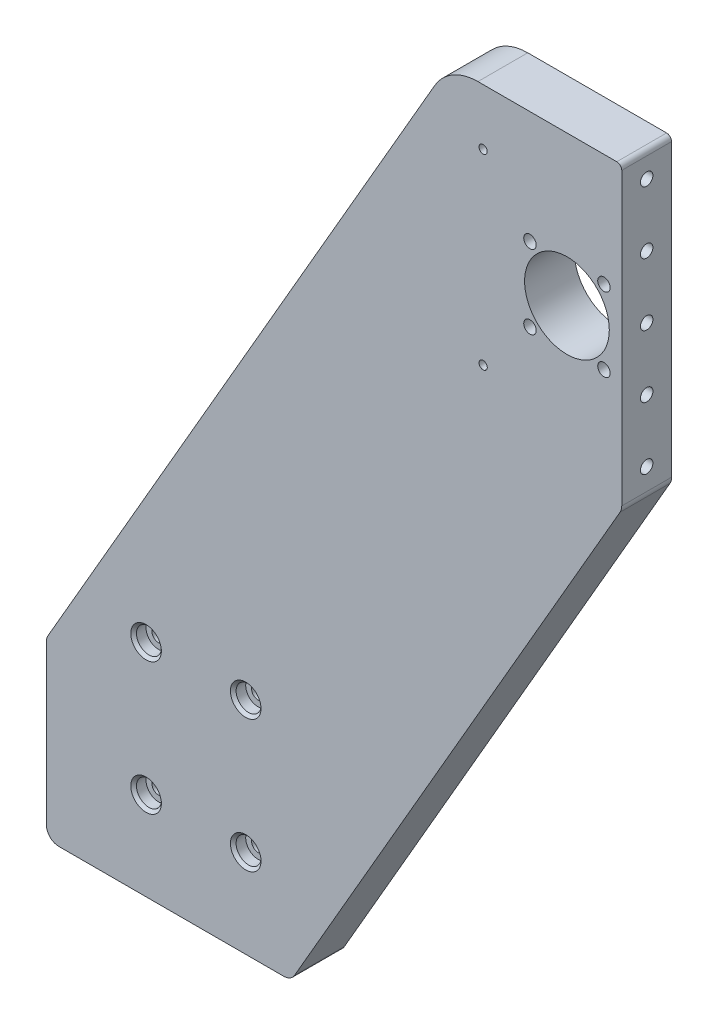
SolidWorks part; units mm, degrees
ref_plane "Piano frontale" through (0, 0, 0) normal (0, 0, 1) x (1, 0, 0)
ref_plane "Piano superiore" through (0, 0, 0) normal (0, 1, 0) x (1, 0, 0)
ref_plane "Piano destro" through (0, 0, 0) normal (1, 0, 0) x (0, 0, -1)
sketch "Schizzo1" plane through (0, 0, 0) normal (0, 0, 1) x (1, 0, 0)
  line L0 (5, 0) -> (95.2628, 0)
  line L1 (99.5929, 2.5) -> (230.2702, 228.8397)
  line L2 (230.9401, 231.3397) -> (230.9401, 348)
  line L3 (228.9401, 350) -> (173.2051, 350)
  line L4 (0, 68.6603) -> (0, 5)
  line L5 (155.8846, 340) -> (0.6699, 71.1603)
  line L9 (208.9401, 290) -> (194.0909, 304.8492) construction
  line L10 (208.9401, 290) -> (187.9401, 290) construction
  line L11 (208.9401, 290) -> (208.9401, 311) construction
  line L12 (50.1314, 0) -> (50.1314, 156.8301) construction
  circle A4 centre (208.9401, 290) radius 17
  circle A5 centre (208.9401, 290) radius 21 construction
  arc A6 (99.5929, 2.5) -> (95.2628, 0) centre (95.2628, 5) cw
  arc A7 (5, 0) -> (0, 5) centre (5, 5) cw
  arc A8 (0, 68.6603) -> (0.6699, 71.1603) centre (5, 68.6603) cw
  arc A9 (230.9401, 231.3397) -> (230.2702, 228.8397) centre (225.9401, 231.3397) cw
  arc A10 (230.9401, 348) -> (228.9401, 350) centre (228.9401, 348) ccw
  arc A11 (173.2051, 350) -> (155.8846, 340) centre (173.2051, 330) ccw
  circle A14 centre (223.7894, 304.8492) radius 2.5
  circle A15 centre (223.7894, 275.1508) radius 2.5
  circle A18 centre (194.0909, 275.1508) radius 2.5
  circle A19 centre (194.0909, 304.8492) radius 2.5
  point P27 (194.0909, 304.8492)
  point P28 (223.7894, 304.8492)
  point P29 (223.7894, 275.1508)
  point P30 (194.0909, 275.1508)
  point P31 (230.9401, 350)
  point P39 (0, 0)
  point P42 (0, 70)
  point P45 (230.9401, 230)
  point P48 (230.9401, 350)
  dimension "D6" = 60
  dimension "D9" = 34
  dimension "D11" = 45
  dimension "D14" = 5
  dimension "D15" = 5
  dimension "D17" = 42
  dimension "D12" = 2
  dimension "D1" = 120
  dimension "D2" = 120
  dimension "D3" = 70
  dimension "D4" = 350
  dimension "D5" = 120
  dimension "D10" = 22
extrude "Estrusione-Estrusione2" add sketch "Schizzo1" against normal blind 20
sketch "Sketch1" plane through (0, 0, 0) normal (0, -1, 0) x (1, 0, 0)
  line L0 (5, -10) -> (95.2628, -10) construction
  line L1 (5, -20) -> (5, 0) construction
  line L2 (95.2628, -20) -> (95.2628, 0) construction
  line L3 (50.1314, 0) -> (50.1314, -20) construction
  line L4 (5, 0) -> (95.2628, 0) construction
  line L5 (5, -20) -> (95.2628, -20) construction
  point P12 (50.1314, -10)
  point P13 (85.1314, -10)
  point P14 (15.1314, -10)
  dimension "D1" = 35
hole_wizard "M5 Tapped Hole1" positions "3DSketch1" profile "Sketch2" tap size "M5" standard "ISO"
sketch3d "3DSketch1"
  point P0 (50.1314, 0, -10)
  point P3 (85.1314, 0, -10)
  point P6 (15.1314, 0, -10)
sketch "Sketch2" plane through (50.1314, 0, -10) normal (1, 0, 0) x (0, 0, -1)
  line L0 (0, 0) -> (0, 18.6618)
  line L1 (0, 18.6618) -> (2.1, 17.4)
  line L2 (2.1, 17.4) -> (2.1, 0)
  line L5 (2.1, 0) -> (0, 0)
  line L10 (0, 18.6618) -> (-2.1, 17.4) construction
  line L11 (0, -6.35) -> (0, 107.95) construction
  dimension "Tap Drill Dia." = 4.2
  dimension "Tap Drill Depth" = 17.4
  dimension "Drill Angle" = 118
sketch "Sketch3" plane through (0, 0, 0) normal (0, 0, 1) x (1, 0, 0)
  line L0 (0, 68.6603) -> (0, 5) construction
  point P0 (40, 88.5)
  point P1 (80, 88.5)
  point P2 (80, 35.5)
  point P3 (40, 35.5)
  dimension "D1" = 40
  dimension "D2" = 53
  dimension "D3" = 40
hole_wizard "CBORE for M5 SHCS1" positions "3DSketch3" profile "Sketch5" counterbore size "M5" standard "ANSI Metric" end condition through all
sketch3d "3DSketch3"
  point P0 (80, 88.5, 0)
  point P3 (80, 35.5, 0)
  point P6 (40, 35.5, 0)
  point P9 (40, 88.5, 0)
sketch "Sketch5" plane through (80, 88.5, 0) normal (1, 0, 0) x (0, -1, 0)
  line L0 (0, 0) -> (0, 20)
  line L1 (0, 20) -> (2.65, 20)
  line L3 (2.65, 20) -> (2.65, 5)
  line L4 (5, 5) -> (2.65, 5)
  line L5 (5, 5) -> (5, 1.145)
  line L6 (5, 1.145) -> (6.145, 0)
  line L7 (6.145, 0) -> (0, 0)
  line L8 (-5, 1.145) -> (-6.145, 0) construction
  line L11 (0, -6.35) -> (0, 107.95) construction
  dimension "Thru Hole Dia." = 5.3
  dimension "Thru Hole Depth" = 20
  dimension "C'Bore Dia." = 10
  dimension "C'Bore Depth" = 5
  dimension "Near C'Sink Dia." = 12.29
  dimension "Near C'Sink Angle" = 90
sketch "Sketch7" plane through (230.9401, 0, 0) normal (1, 0, 0) x (0, 0, -1)
  point P0 (10, 340)
  point P1 (10, 315)
  point P2 (10, 290)
  point P3 (10, 265)
  point P4 (10, 240)
hole_wizard "M6 Tapped Hole1" positions "3DSketch6" profile "Sketch12" tap size "M6" standard "ISO"
sketch3d "3DSketch6"
  point P0 (230.9401, 340, -10)
  point P3 (230.9401, 315, -10)
  point P6 (230.9401, 290, -10)
  point P9 (230.9401, 265, -10)
  point P12 (230.9401, 240, -10)
sketch "Sketch12" plane through (230.9401, 340, -10) normal (0, 1, 0) x (0, 0, -1)
  line L0 (0, 0) -> (0, 20.5022)
  line L1 (0, 20.5022) -> (2.5, 19)
  line L2 (2.5, 19) -> (2.5, 0)
  line L5 (2.5, 0) -> (0, 0)
  line L10 (0, 20.5022) -> (-2.5, 19) construction
  line L11 (0, -6.35) -> (0, 107.95) construction
  dimension "Tap Drill Dia." = 5
  dimension "Tap Drill Depth" = 19
  dimension "Drill Angle" = 118
sketch "Sketch13" plane through (0, 0, 0) normal (0, 0, 1) x (1, 0, 0)
  point P0 (175.2886, 327.5068)
  point P1 (175.3131, 252.4712)
hole_wizard "M4 Tapped Hole1" positions "3DSketch10" profile "Sketch16" tap size "M4" standard "ISO" end condition through all
sketch3d "3DSketch10"
  point P0 (175.2886, 327.5068, 0)
  point P3 (175.3131, 252.4712, 0)
sketch "Sketch16" plane through (175.2886, 327.5068, 0) normal (1, 0, 0) x (0, -1, 0)
  line L0 (0, 0) -> (0, 20)
  line L1 (0, 20) -> (1.65, 20)
  line L2 (1.65, 20) -> (1.65, 0)
  line L5 (1.65, 0) -> (0, 0)
  line L11 (0, -6.35) -> (0, 107.95) construction
  dimension "Thread Major Dia." = 3.3
  dimension "Thru Tap Drill Depth" = 20
